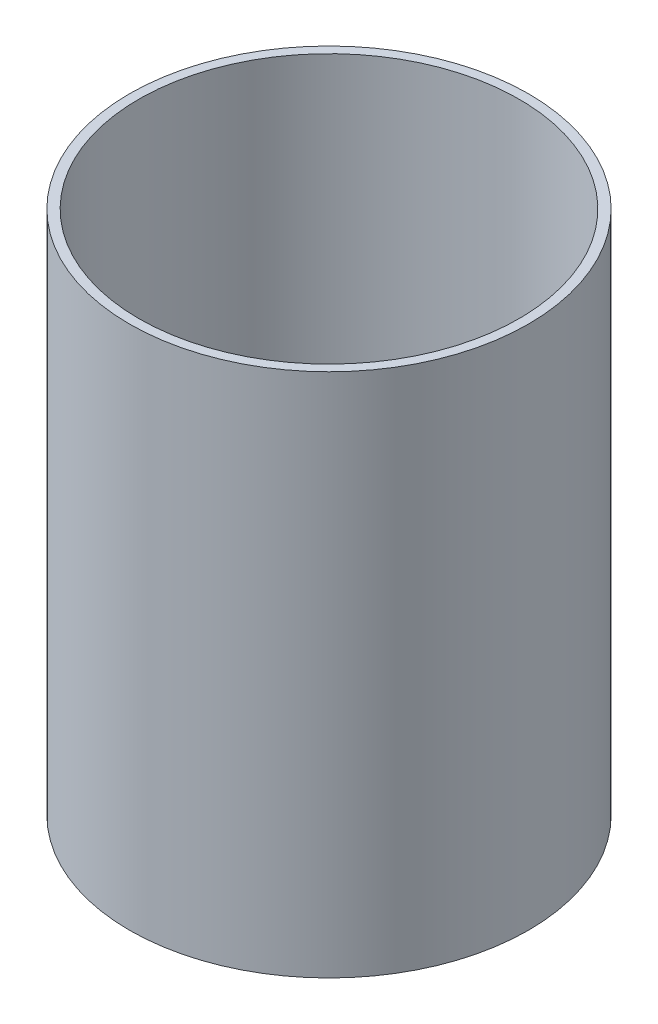
SolidWorks part; units mm, degrees
ref_plane "Front Plane" through (0, 0, 0) normal (0, 0, 1) x (1, 0, 0)
ref_plane "Top Plane" through (0, 0, 0) normal (0, 1, 0) x (1, 0, 0)
ref_plane "Right Plane" through (0, 0, 0) normal (1, 0, 0) x (0, 0, -1)
sketch "Sketch1" plane through (0, 0, 0) normal (0, 1, 0) x (1, 0, 0)
  circle A0 centre (0, 0) radius 25.35
  circle A1 centre (0, 0) radius 26.6
  dimension "D1" = 53.2
  dimension "D2" = 50.7
extrude "Boss-Extrude1" add sketch "Sketch1" along normal blind 70
